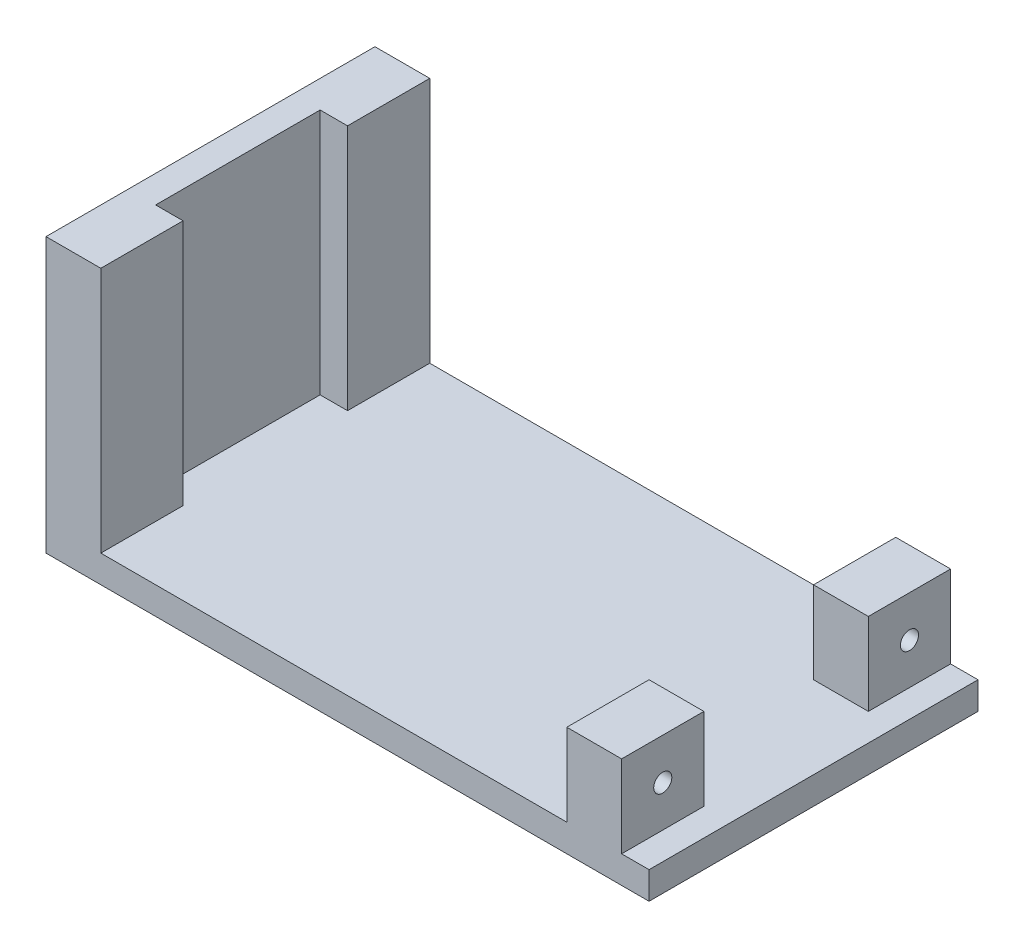
SolidWorks part; units mm, degrees
ref_plane "Alzado" through (0, 0, 0) normal (0, 0, 1) x (1, 0, 0)
ref_plane "Planta" through (0, 0, 0) normal (0, 1, 0) x (1, 0, 0)
ref_plane "Vista lateral" through (0, 0, 0) normal (1, 0, 0) x (0, 0, -1)
sketch "Croquis1" plane through (0, 0, 0) normal (0, 1, 0) x (1, 0, 0)
  line L1 (0, 0) -> (110, 0)
  line L2 (0, 0) -> (0, 60)
  line L3 (0, 60) -> (110, 60)
  line L4 (110, 0) -> (110, 60)
  dimension "D1" = 110
  dimension "D2" = 60
extrude "Saliente-Extruir1" add sketch "Croquis1" along normal blind 5
sketch "Croquis2" plane through (0, 5, 0) normal (0, 1, 0) x (1, 0, 0)
  line L0 (110, 60) -> (0, 60) construction
  line L1 (0, 0) -> (10, 0)
  line L2 (0, 0) -> (0, 60)
  line L3 (0, 60) -> (10, 60)
  line L4 (10, 0) -> (10, 15)
  line L5 (10, 45) -> (5, 45)
  line L6 (5, 45) -> (5, 15)
  line L7 (5, 15) -> (10, 15)
  line L8 (10, 45) -> (10, 60)
  dimension "D1" = 10
  dimension "D2" = 15
  dimension "D3" = 15
  dimension "D4" = 30
  dimension "D5" = 5
extrude "Saliente-Extruir2" add sketch "Croquis2" along normal blind 45
sketch "Croquis3" plane through (0, 0, 0) normal (-1, 0, 0) x (0, 0, 1)
  line L0 (-60, 50) -> (-52.5, 50) construction
  line L1 (-60, 50) -> (0, 50) construction
  line L2 (0, 0) -> (-7.5, 0) construction
  line L3 (-60, 0) -> (0, 0) construction
  line L4 (-7.5, 0) -> (-7.5, 5) construction
  line L5 (-7.5, 5) -> (-7.5, 10) construction
  line L6 (-52.5, 50) -> (-52.5, 40) construction
  point P14 (-52.5, 40)
  point P15 (-52.5, 40)
  point P16 (-7.5, 10)
  dimension "D1" = 7.5
  dimension "D2" = 7.5
  dimension "D3" = 5
  dimension "D4" = 5
  dimension "D5" = 10
sketch "Croquis4" plane through (0, 5, 0) normal (0, 1, 0) x (1, 0, 0)
  line L1 (110, 60) -> (95, 60)
  line L2 (110, 60) -> (110, 45)
  line L3 (110, 45) -> (95, 45)
  line L4 (95, 60) -> (95, 45)
  line L5 (110, 0) -> (95, 0)
  line L6 (110, 0) -> (110, 15)
  line L7 (110, 15) -> (95, 15)
  line L8 (95, 0) -> (95, 15)
  dimension "D1" = 15
  dimension "D2" = 15
  dimension "D3" = 15
  dimension "D4" = 15
extrude "Saliente-Extruir3" add sketch "Croquis4" along normal blind 15
sketch "Croquis5" plane through (110, 0, 0) normal (1, 0, 0) x (0, 0, -1)
  line L2 (15, 5) -> (0, 5)
  line L3 (15, 5) -> (15, 20)
  line L4 (15, 20) -> (0, 20)
  line L5 (0, 5) -> (0, 20)
  line L6 (45, 5) -> (60, 5)
  line L7 (45, 5) -> (45, 20)
  line L8 (45, 20) -> (60, 20)
  line L9 (60, 5) -> (60, 20)
extrude "Cortar-Extruir1" cut sketch "Croquis5" against normal blind 5
sketch "Croquis6" plane through (105, 0, 0) normal (1, 0, 0) x (0, 0, -1)
  line L0 (7.5, 5) -> (7.5, 12.5) construction
  line L1 (7.5, 12.5) -> (52.5, 12.5) construction
  line L2 (60, 5) -> (60, 20) construction
  point P7 (7.5, 12.5)
  point P8 (52.5, 12.5)
  dimension "D1" = 7.5
  dimension "D2" = 7.5
hole_wizard "Taladro roscado M41" positions "Croquis9" profile "Croquis10" tap size "M4" standard "DIN"
sketch "Croquis9" plane through (105, 0, 0) normal (1, 0, 0) x (0, 0, -1)
  point P0 (7.5, 12.5)
  point P3 (52.5, 12.5)
sketch "Croquis10" plane through (105, 12.5, -7.5) normal (0, 1, 0) x (0, 0, -1)
  line L0 (0, 0) -> (0, 15)
  line L1 (0, 15) -> (1.65, 14.0086)
  line L2 (1.65, 14.0086) -> (1.65, 0)
  line L5 (1.65, 0) -> (0, 0)
  line L10 (0, 15) -> (-1.65, 14.0086) construction
  line L11 (0, -6.35) -> (0, 107.95) construction
  dimension "Diámetro de perforador para roscar" = 3.3
  dimension "Profundidad de perforador para roscar" = 15
  dimension "Ángulo de perforador" = 118
cosmetic thread "Rosca de taladro1" parameters "D1"=8, "D2"=4
cosmetic thread "Rosca de taladro2" parameters "D1"=8, "D2"=4
